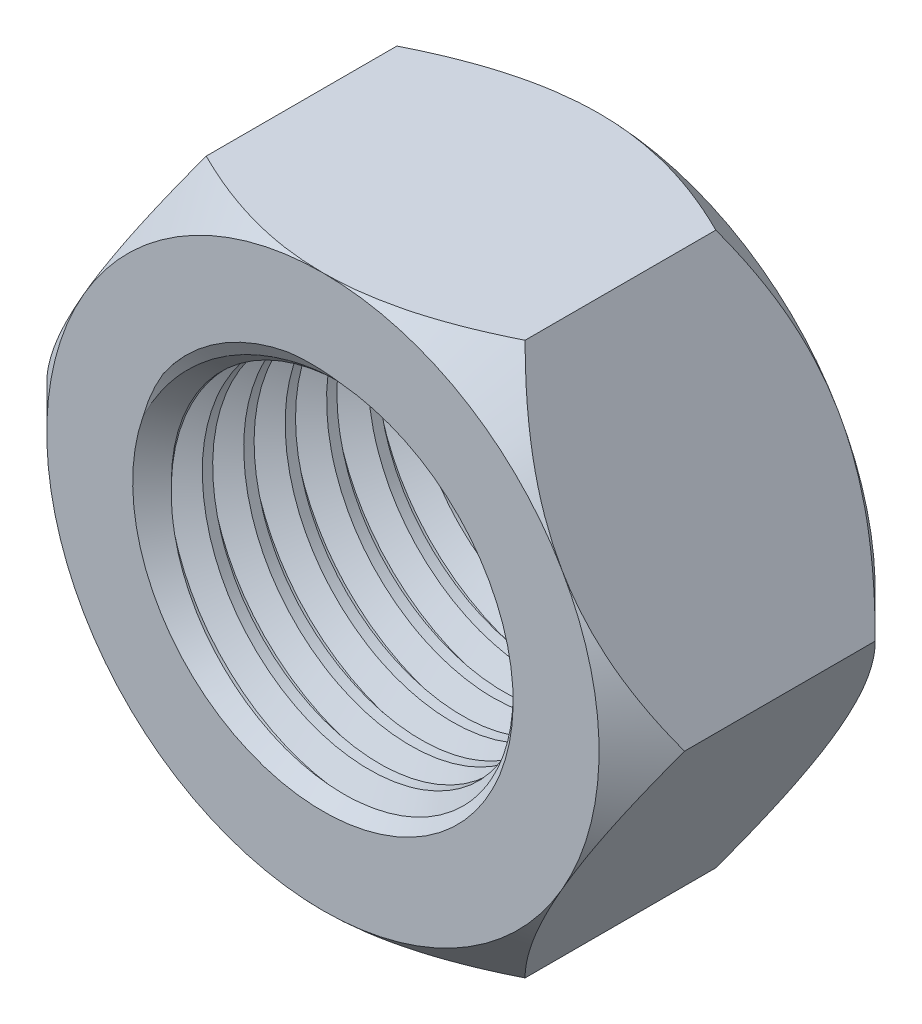
SolidWorks part; units mm, degrees
material "AISI 304"
ref_plane "Front Plane" through (0, 0, 0) normal (0, 0, 1) x (1, 0, 0)
ref_plane "Top Plane" through (0, 0, 0) normal (0, 1, 0) x (1, 0, 0)
ref_plane "Right Plane" through (0, 0, 0) normal (1, 0, 0) x (0, 0, -1)
sketch "Sketch1" plane through (0, 0, 0) normal (0, 0, 1) x (1, 0, 0)
  line L1 (5.7735, -10) -> (11.547, 0)
  line L2 (11.547, 0) -> (5.7735, 10)
  line L3 (5.7735, 10) -> (-5.7735, 10)
  line L4 (-5.7735, 10) -> (-11.547, 0)
  line L5 (-11.547, 0) -> (-5.7735, -10)
  line L6 (-5.7735, -10) -> (5.7735, -10)
  circle A0 centre (0, 0) radius 10 construction
  dimension "D1" = 20
extrude "Boss-Extrude1" add sketch "Sketch1" along normal mid plane 10
sketch "Sketch2" plane through (0, 0, 5) normal (0, 0, 1) x (1, 0, 0)
  line L2 (-5.7735, 10) -> (-11.547, 0) construction
  circle A0 centre (0, 0) radius 10
extrude "Cut-Extrude1" cut sketch "Sketch2" against normal through all draft 45 flip side to cut
mirror "Mirror1" about plane through (0, 0, 0) normal (0, 0, 1) of "Cut-Extrude1"
sketch "Sketch3" plane through (0, 0, 5) normal (0, 0, 1) x (1, 0, 0)
  circle A0 centre (0, 0) radius 6.1881
  dimension "D1" = 12.3762
extrude "Cut-Extrude2" cut sketch "Sketch3" against normal through all
chamfer "Chamfer1" distance 0.7 angle 45 2 edges at (6.1881, 0, -5) (6.1881, 0, 5)
thread "Thread1" pitch 1.5 method cut profile "Thread Profile1" start angle 0, offset 3, length 0, pitch 1.5, diameter 12.3762
ref_plane "Plane1" through (-6.1881, 0, 7.3) normal (0, -1, 0) x (-1, 0, 0)
sketch "Thread Profile1" plane through (-6.1881, 0, 7.3) normal (0, -1, 0) x (-1, 0, 0)
  line L0 (0, 0) -> (0, 1.5) construction
  line L1 (0, 0) -> (0.8119, 0.4687)
  line L2 (0.8119, 0.4687) -> (0.8119, 0.6562)
  line L3 (0.8119, 0.6562) -> (0, 1.125)
  line L4 (0.8119, 0.5625) -> (0, 0.5625) construction
  line L11 (0, 0) -> (0, 1.125)
  point P2 (0, 0)
  dimension "Pitch" = 1.5
  dimension "Profile_Angle" = 60
  dimension "Profile_Land" = 0.1875
  dimension "Profile_Height" = 0.8119
